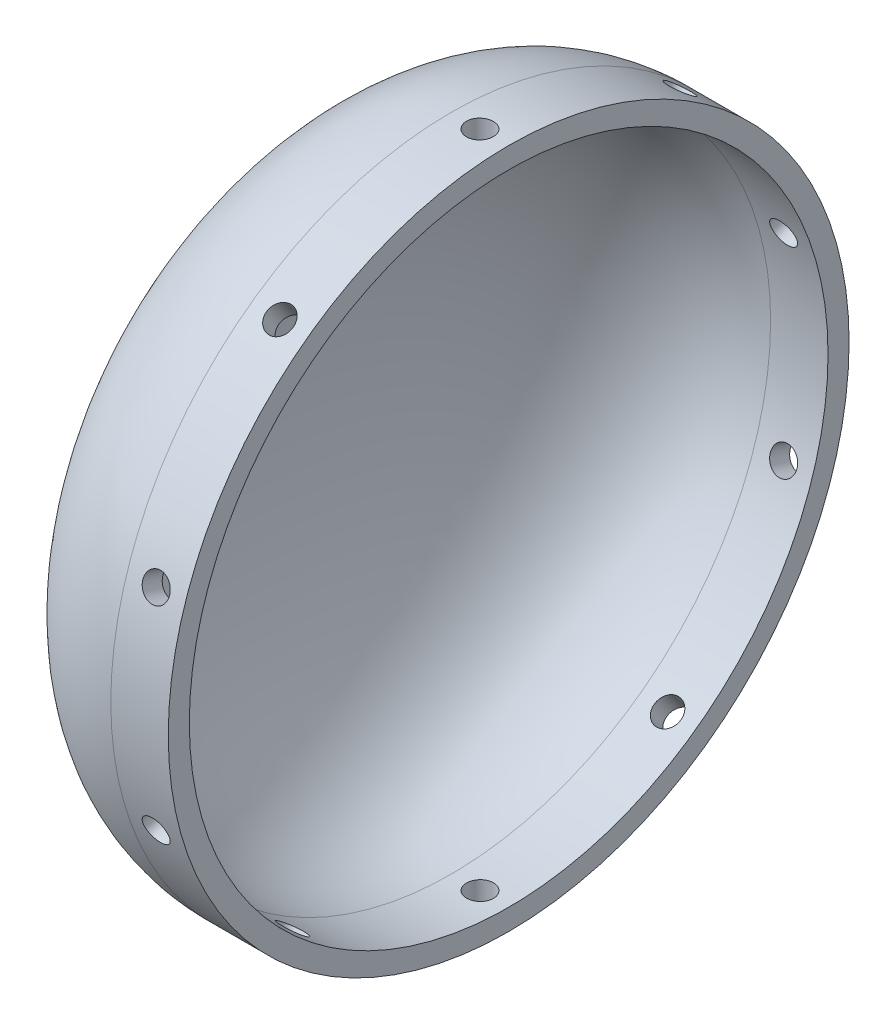
SolidWorks part; units mm, degrees
material "A105 N"
ref_plane "Front Plane" through (0, 0, 0) normal (0, 0, 1) x (1, 0, 0)
ref_plane "Top Plane" through (0, 0, 0) normal (0, 1, 0) x (1, 0, 0)
ref_plane "Right Plane" through (0, 0, 0) normal (1, 0, 0) x (0, 0, -1)
sketch "Sketch1" plane through (0, 0, 0) normal (0, 0, 1) x (1, 0, 0)
  line L0 (-30, 177.8) -> (0, 177.8)
  line L1 (0, 0) -> (-347.074, 0) construction
  line L2 (-30, 166.8) -> (0, 166.8)
  line L3 (-130, 0) -> (-119, 0)
  line L4 (0, 177.8) -> (0, 166.8)
  spline S0 degree 3 poles (-130, 0) (-130, 90.9187) (-104.7243, 177.8) (-30, 177.8) knots 0 0 0 0 1 1 1 1
  spline S1 degree 1 poles (-119, 0) (-30, 166.8) knots 0 0 1 1 construction
  spline S2 degree 3 poles (-119, 0) (-119, 2.7716) (-118.9517, 8.325) (-118.6568, 19.3485) (-117.9062, 32.9785) (-116.364, 48.9508) (-113.4156, 69.5658) (-107.9932, 93.7237) (-98.566, 119.0692) (-88.275, 136.2876) (-78.6409, 147.3336) (-70.7141, 154.2114) (-62.0424, 159.6639) (-54.1038, 163.0097) (-47.2416, 164.9386) (-41.8192, 165.9971) (-37.0455, 166.5409) (-33.0815, 166.7624) (-31.0208, 166.8) (-30, 166.8) knots 0 0 0 0 0.03125 0.0625 0.125 0.1875 0.25 0.375 0.5 0.625 0.6875 0.75 0.8125 0.875 0.90625 0.9375 0.96875 0.984375 1 1 1 1
  dimension "D1" = 177.8
  dimension "D4" = 11
  dimension "D2" = 100
  dimension "D3" = 30
revolve "Revolve1" add sketch "Sketch1" angle 360 about L1
sketch "Sketch2" plane through (0, 0, 0) normal (0, 1, 0) x (1, 0, 0)
  line L0 (0, 0) -> (-15, 0) construction
  circle A0 centre (-15, 0) radius 7
  dimension "D2" = 14
  dimension "D1" = 15
extrude "Cut-Extrude1" cut sketch "Sketch2" against normal through all contours A0
cosmetic thread "Cosmetic Thread1" parameters "D1"=5, "D2"=16
pattern_circular "CirPattern1" count 10 over 360 about axis through (-30, 0, 0) along (1, 0, 0) of "Cut-Extrude1"
cosmetic thread "Cosmetic Thread2" parameters "D1"=5, "D2"=16
cosmetic thread "Cosmetic Thread3" parameters "D1"=5, "D2"=16
cosmetic thread "Cosmetic Thread4" parameters "D1"=5, "D2"=16
cosmetic thread "Cosmetic Thread5" parameters "D1"=5, "D2"=16
cosmetic thread "Cosmetic Thread6" parameters "D1"=5, "D2"=16
cosmetic thread "Cosmetic Thread7" parameters "D1"=5, "D2"=16
cosmetic thread "Cosmetic Thread8" parameters "D1"=5, "D2"=16
cosmetic thread "Cosmetic Thread9" parameters "D1"=5, "D2"=16
cosmetic thread "Cosmetic Thread10" parameters "D1"=5, "D2"=16
